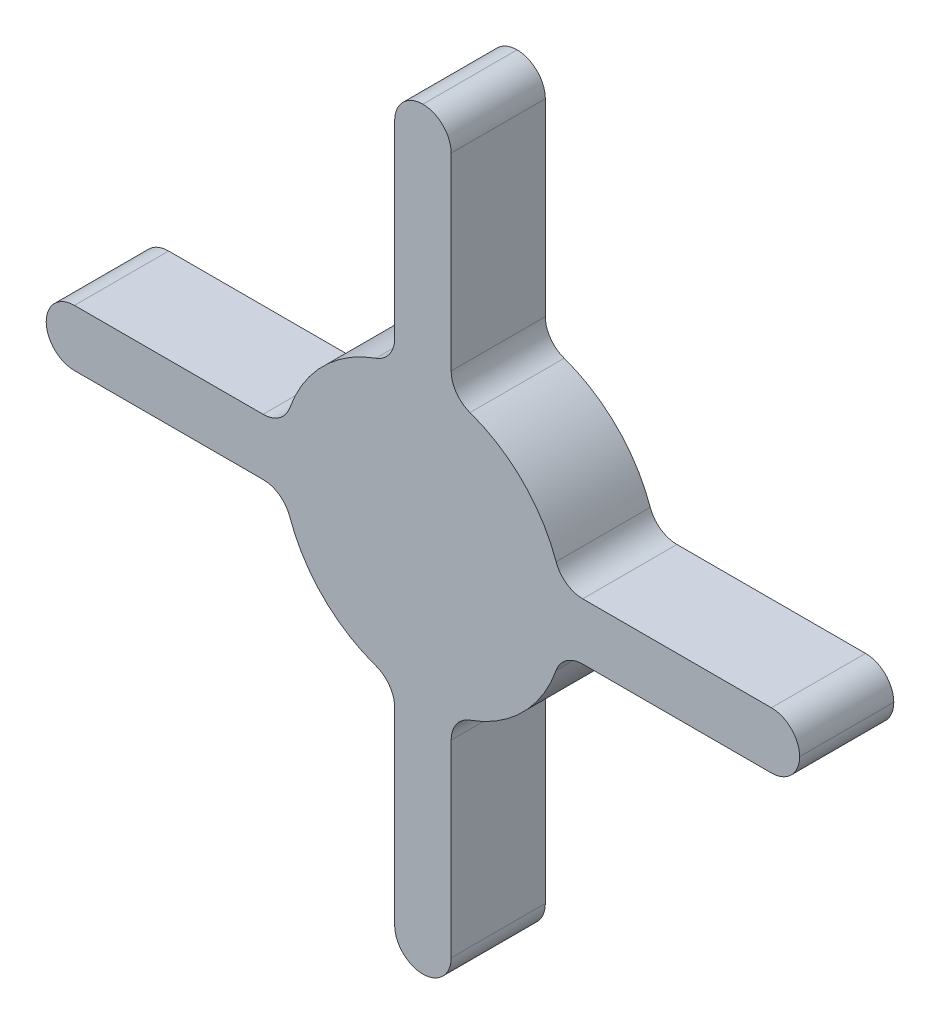
SolidWorks part; units mm, degrees
ref_plane "Front Plane" through (0, 0, 0) normal (0, 0, 1) x (1, 0, 0)
ref_plane "Top Plane" through (0, 0, 0) normal (0, 1, 0) x (1, 0, 0)
ref_plane "Right Plane" through (0, 0, 0) normal (1, 0, 0) x (0, 0, -1)
sketch "Sketch1" plane through (0, 0, 0) normal (0, 0, 1) x (1, 0, 0)
  line L0 (0, 25.4) -> (0, -25.4) construction
  line L1 (-25.4, 0) -> (25.4, 0) construction
  line L2 (0, 25.4) -> (1.905, 25.4)
  line L3 (1.905, 25.4) -> (1.905, 1.905)
  line L4 (1.905, 1.905) -> (25.4, 1.905)
  line L5 (25.4, 1.905) -> (25.4, 0)
  line L6 (25.4, 0) -> (25.4, -1.905)
  line L7 (25.4, -1.905) -> (1.905, -1.905)
  line L8 (1.905, -1.905) -> (1.905, -25.4)
  line L9 (1.905, -25.4) -> (0, -25.4)
  line L10 (0, -25.4) -> (-1.905, -25.4)
  line L11 (-1.905, -25.4) -> (-1.905, -1.905)
  line L12 (-1.905, -1.905) -> (-25.4, -1.905)
  line L13 (-25.4, -1.905) -> (-25.4, 0)
  line L14 (-25.4, 0) -> (-25.4, 1.905)
  line L15 (-25.4, 1.905) -> (-1.905, 1.905)
  line L16 (-1.905, 1.905) -> (-1.905, 25.4)
  line L17 (-1.905, 25.4) -> (0, 25.4)
  dimension "D1" = 50.8
  dimension "D2" = 50.8
  dimension "D3" = 1.905
  dimension "D4" = 23.495
  dimension "D5" = 1.905
  dimension "D6" = 1.905
  dimension "D7" = 1.905
  dimension "D8" = 1.905
  dimension "D9" = 1.905
  dimension "D10" = 1.905
extrude "Boss-Extrude1" add sketch "Sketch1" along normal blind 6.35
sketch "Sketch2" plane through (0, 0, 0) normal (0, 0, 1) x (1, 0, 0)
  circle A0 centre (0, 0) radius 9.525
  dimension "D1" = 19.05
extrude "Boss-Extrude2" add sketch "Sketch2" along normal blind 6.35
fillet "Fillet1" radius 1.905 16 edges at (-9.3326, -1.905, 3.175) (-1.905, -9.3326, 3.175) (-9.3326, 1.905, 3.175) (-1.905, 9.3326, 3.175) (1.905, 9.3326, 3.175) (9.3326, 1.905, 3.175) (9.3326, -1.905, 3.175) (1.905, -9.3326, 3.175) (25.4, 1.905, 3.175) (25.4, -1.905, 3.175) (1.905, -25.4, 3.175) (-1.905, -25.4, 3.175) (-25.4, -1.905, 3.175) (-25.4, 1.905, 3.175) (-1.905, 25.4, 3.175) (1.905, 25.4, 3.175)
